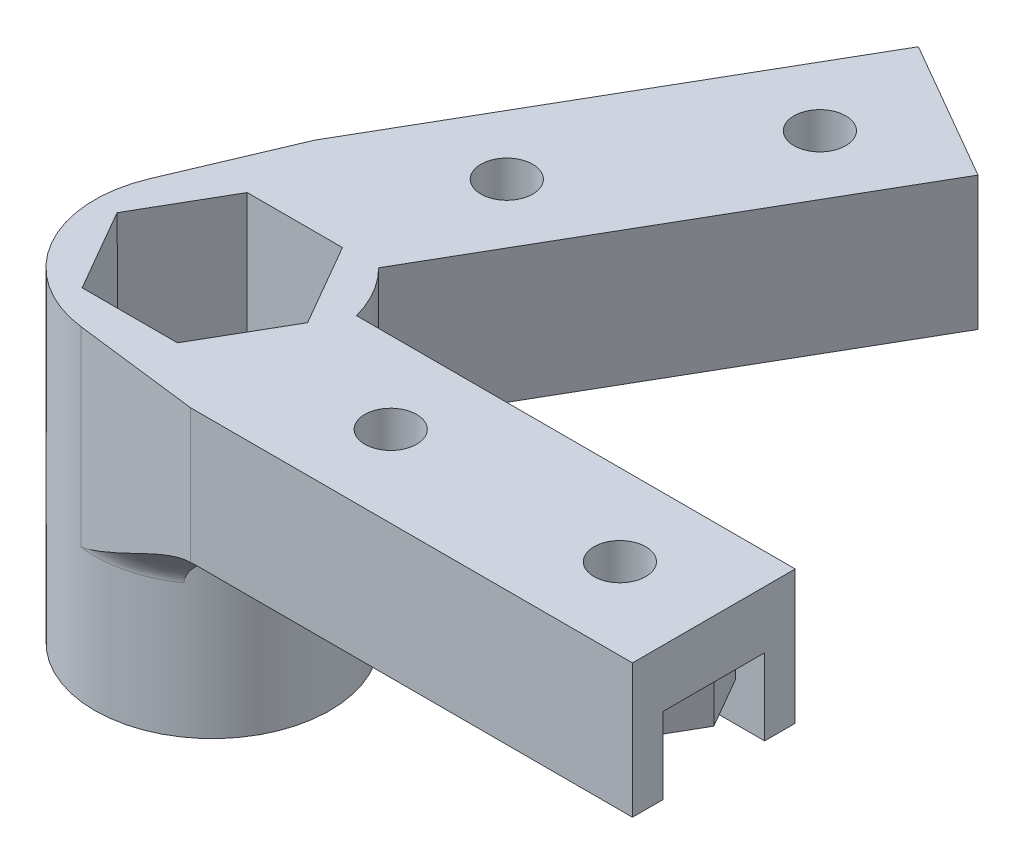
SolidWorks part; units mm, degrees
note: '?' marks a value the reader was unsure of.
ref_plane "Front Plane" through (0, 0, 0) normal (0, 0, 1) x (1, 0, 0)
ref_plane "Top Plane" through (0, 0, 0) normal (0, 1, 0) x (1, 0, 0)
ref_plane "Right Plane" through (0, 0, 0) normal (1, 0, 0) x (0, 0, -1)
sketch "Sketch1" plane through (0, 0, 0) normal (0, 1, 0) x (1, 0, 0)
  line L0 (57.15, 2.54) -> (57.15, -10.9855)
  line L2 (9.4434, 2.54) -> (57.15, 2.54)
  line L3 (-1.197, -9.7055) -> (9.1817, -10.9855)
  line L4 (9.1817, -10.9855) -> (57.15, -10.9855)
  circle A0 centre (0, 0) radius 5.0165
  arc A1 (9.4434, 2.54) -> (-1.197, -9.7055) centre (0, 0) ccw
  circle A4 centre (0, 0) radius 9.779 construction
  dimension "D1" = 4.7625
  dimension "D3" = 10.033
  dimension "D5" = 2.54
  dimension "D2" = 57.15
  dimension "D4" = 13.5255
extrude "Boss-Extrude1" add sketch "Sketch1" along normal blind 26.9875
sketch "Sketch18" plane through (0, 0, 0) normal (0, -1, 0) x (1, 0, 0)
  line L2 (57.15, 8.4455) -> (57.15, 0)
  line L3 (57.15, 0) -> (9.779, 0)
  line L6 (9.3378, 8.4455) -> (5.6391, 7.9893)
  line L7 (-1.197, 9.7055) -> (9.1817, 10.9855) construction
  line L9 (57.15, -2.54) -> (9.4434, -2.54) construction
  line L10 (57.15, 10.9855) -> (57.15, -2.54) construction
  line L11 (57.15, 8.4455) -> (9.3378, 8.4455)
  circle A2 centre (0, 0) radius 9.779
  arc A3 (9.779, 0) -> (5.6391, 7.9893) centre (0, 0) ccw
  dimension "D1" = 8.4455
  dimension "D2" = 2.54
  dimension "D3" = 4.7625
  dimension "D4" = 2.54
extrude "Cut-Extrude7" cut sketch "Sketch18" against normal blind 22.225
hole_wizard "#6 Clearance Hole1" positions "Sketch19" profile "Sketch20" hole size "#6" standard "ANSI Inch" end condition through all
sketch "Sketch19" plane through (0, 22.225, 0) normal (0, -1, 0) x (-1, 0, 0)
  line L0 (-9.779, 0) -> (-57.15, 0) construction
  point P0 (-19.05, -4.2227)
  point P2 (-38.1, -4.2227)
  dimension "D1" = 19.05
  dimension "D2" = 19.05
  dimension "D3" = 4.2227
sketch "Sketch20" plane through (19.05, 22.225, 4.2227) normal (1, 0, 0) x (0, 0, -1)
  line L0 (0, 0) -> (0, 4.7625)
  line L1 (0, 4.7625) -> (2.1526, 4.7625)
  line L2 (2.1526, 4.7625) -> (2.1526, 0)
  line L5 (2.1526, 0) -> (0, 0)
  line L11 (0, -6.35) -> (0, 107.95) construction
  dimension "Thru Hole Dia." = 4.3053
  dimension "Thru Hole Depth" = 4.7625
sketch "Sketch21" plane through (0, 22.225, 0) normal (0, -1, 0) x (1, 0, 0)
  line L1 (23.926, 4.2227) -> (21.488, 8.4455)
  line L2 (21.488, 8.4455) -> (16.612, 8.4455)
  line L3 (16.612, 8.4455) -> (14.174, 4.2227)
  line L4 (14.174, 4.2227) -> (16.612, 0)
  line L5 (16.612, 0) -> (21.488, 0)
  line L6 (21.488, 0) -> (23.926, 4.2227)
  line L7 (42.976, 4.2227) -> (40.538, 8.4455)
  line L8 (40.538, 8.4455) -> (35.662, 8.4455)
  line L9 (35.662, 8.4455) -> (33.224, 4.2227)
  line L10 (33.224, 4.2227) -> (35.662, 0)
  line L11 (35.662, 0) -> (40.538, 0)
  line L12 (40.538, 0) -> (42.976, 4.2227)
  line L13 (14.4123, 9.7155) -> (11.241, 4.2227)
  line L14 (11.241, 4.2227) -> (14.4123, -1.27)
  line L16 (23.6877, -1.27) -> (26.859, 4.2227)
  line L17 (26.859, 4.2227) -> (23.6877, 9.7155)
  line L19 (33.4623, 9.7155) -> (30.291, 4.2227)
  line L20 (30.291, 4.2227) -> (33.4623, -1.27)
  line L22 (42.7377, -1.27) -> (45.909, 4.2227)
  line L23 (45.909, 4.2227) -> (42.7377, 9.7155)
  line L25 (22.9545, 10.9855) -> (15.1455, 10.9855) construction
  line L26 (15.1455, -2.54) -> (22.9545, -2.54) construction
  line L27 (34.1955, -2.54) -> (42.0045, -2.54) construction
  line L28 (42.0045, 10.9855) -> (34.1955, 10.9855) construction
  line L29 (23.6877, 9.7155) -> (14.4123, 9.7155)
  line L30 (14.4123, -1.27) -> (23.6877, -1.27)
  line L31 (33.4623, -1.27) -> (42.7377, -1.27)
  line L32 (42.7377, 9.7155) -> (33.4623, 9.7155)
  line L33 (21.488, 9.7155) -> (16.612, 9.7155) construction
  line L34 (16.612, -1.27) -> (21.488, -1.27) construction
  line L35 (35.662, -1.27) -> (40.538, -1.27) construction
  line L36 (40.538, 9.7155) -> (35.662, 9.7155) construction
  line L37 (15.1455, 10.9855) -> (11.241, 4.2227) construction
  line L38 (26.859, 4.2227) -> (22.9545, 10.9855) construction
  line L39 (22.9545, -2.54) -> (26.859, 4.2227) construction
  line L40 (11.241, 4.2227) -> (15.1455, -2.54) construction
  line L41 (30.291, 4.2227) -> (34.1955, -2.54) construction
  line L42 (42.0045, -2.54) -> (45.909, 4.2227) construction
  line L43 (45.909, 4.2227) -> (42.0045, 10.9855) construction
  line L44 (34.1955, 10.9855) -> (30.291, 4.2227) construction
  circle A0 centre (19.05, 4.2227) radius 4.2228 construction
  circle A1 centre (38.1, 4.2227) radius 4.2227 construction
  dimension "D3" = 8.4455
  dimension "D1" = 2.54
  dimension "D2" = 1.27
extrude "Boss-Extrude6" add sketch "Sketch21" along normal blind 3.175
ref_axis "Axis1" through (0, 26.9875, 0) along (0, -1, 0)?
ref_plane "Plane1" through (0, 0, 0) normal (0.5, 0, 0.866) x (0, -1, 0)
mirror "Mirror1" about plane through (0, 0, 0) normal (0.5, 0, 0.866) of bodies 121 106 117
sketch "Sketch9" plane through (0, 0, 0) normal (0, 0, 1) x (1, 0, 0)
  line L1 (0, 26.9875) -> (0, 0) construction
  line L2 (57.15, 26.9875) -> (9.4434, 26.9875) construction
  circle A0 centre (63.5, 0) radius 26.9875
  dimension "D1" = 63.5
  dimension "D2" = 53.975
sketch "Sketch10" plane through (0, 0, -2.54) normal (0, 0, -1) x (-1, 0, 0)
  line L5 (-57.15, 26.9875) -> (-9.4434, 26.9875) construction
  line L6 (-57.15, 26.9875) -> (-50.0296, 26.9875)
  line L7 (-57.15, 26.9875) -> (-57.15, 0) construction
  line L8 (-57.15, 26.9875) -> (-57.15, 0)
  line L9 (-57.15, 0) -> (-9.4434, 0) construction
  line L10 (-57.15, 0) -> (-33.3375, 0)
  circle A3 centre (-63.5, 0) radius 30.1625
  arc A4 (-33.3375, 0) -> (-50.0296, 26.9875) centre (-63.5, 0) ccw
  dimension "D1" = 3.175
extrude "Boss-Extrude4" add sketch "Sketch10" along normal blind 15.875
sketch "Sketch11" plane through (0, 0, -2.54) normal (0, 0, -1) x (-1, 0, 0)
  circle A1 centre (-63.5, 0) radius 31.75
  circle A2 centre (-63.5, 0) radius 28.575
  circle A3 centre (-63.5, 0) radius 28.575
  dimension "D1" = 1.5875
  dimension "D2" = 3.175
extrude "Cut-Extrude1" cut sketch "Sketch11" along normal blind 12.7
extrude "Cut-Extrude2" cut sketch "Sketch9" against normal through all and the other way through all
sketch "Sketch13" plane through (0, 0, 0) normal (0, -1, 0) x (1, 0, 0)
  line L0 (28.575, -49.4934) -> (4.8895, -8.4689)
  line L1 (28.575, -49.4934) -> (30.7747, -48.2234)
  line L3 (30.7747, -48.2234) -> (6.9214, -6.9082)
  line L4 (30.7747, -48.2234) -> (6.9214, -6.9082) construction
  line L5 (9.779, 0) -> (30.1625, 0)
  line L7 (30.1625, 0) -> (30.1625, -2.54)
  line L8 (9.4434, -2.54) -> (30.1625, -2.54)
  line L10 (34.925, -2.54) -> (9.4434, -2.54) construction
  line L11 (36.5125, -18.415) -> (36.5125, 0) construction
  line L12 (9.779, 0) -> (36.5125, 0) construction
  line L13 (4.8895, -8.4689) -> (6.8395, -11.8464) construction
  line L14 (28.575, -49.4934) -> (30.7747, -48.2234) construction
  line L16 (-9.0037, -3.8161) -> (-4.9229, -13.4444) construction
  line L17 (-4.9229, -13.4444) -> (19.0613, -54.9861) construction
  line L19 (19.0613, -54.9861) -> (21.261, -53.7161) construction
  line L21 (-9.0037, -3.8161) -> (-4.9229, -13.4444)
  line L22 (-4.9229, -13.4444) -> (19.0613, -54.9861)
  line L24 (19.0613, -54.9861) -> (21.261, -53.7161)
  line L26 (9.3378, 8.4455) -> (5.6391, 7.9893) construction
  line L28 (-1.197, 9.7055) -> (9.1817, 10.9855) construction
  line L29 (57.15, 8.4455) -> (9.3378, 8.4455)
  line L30 (9.3378, 8.4455) -> (5.6391, 7.9893)
  line L31 (9.1817, 10.9855) -> (57.15, 10.9855)
  line L32 (-1.197, 9.7055) -> (9.1817, 10.9855)
  line L33 (57.15, 10.9855) -> (57.15, 8.4455)
  line L35 (9.1817, 10.9855) -> (36.5125, 10.9855) construction
  line L36 (57.15, 10.9855) -> (57.15, -18.415) construction
  line L38 (21.261, -53.7161) -> (-2.6451, -12.3095)
  line L39 (-2.6451, -12.3095) -> (-4.0994, -8.8783) construction
  line L40 (-2.6451, -12.3095) -> (-4.0994, -8.8783)
  arc A0 (4.8895, -8.4689) -> (6.9214, -6.9082) centre (0, 0) ccw
  arc A1 (9.779, 0) -> (9.4434, -2.54) centre (0, 0) cw
  arc A2 (6.9214, -6.9082) -> (9.4434, -2.54) centre (0, 0) ccw construction
  arc A3 (-9.0037, -3.8161) -> (-4.0994, -8.8783) centre (0, 0) ccw
  arc A4 (5.6391, 7.9893) -> (-1.197, 9.7055) centre (0, 0) ccw
  dimension "D1" = 6.35
extrude "Cut-Extrude4" cut sketch "Sketch13" against normal blind 15.875
fillet "Fillet2" radius 4.7625 4 edges at (9.6947, 15.875, -1.281) (5.9568, 15.875, -7.7554) (-7.0235, 15.875, -6.8044) (2.381, 15.875, 9.4847)
sketch "Sketch14" plane through (0, 0, 0) normal (0, 0, 1) x (1, 0, 0)
  line L0 (31.75, 0) -> (30.1625, 0)
  line L2 (30.1625, 15.875) -> (30.1625, 0)
  line L4 (30.1625, 0) -> (36.5125, 0) construction
  line L5 (30.1625, 15.875) -> (30.1625, 0) construction
  line L6 (41.6755, 15.875) -> (9.5275, 15.875) construction
  arc A0 (48.1907, 22.225) -> (36.5125, 0) centre (63.5, 0) ccw construction
  arc A1 (33.6678, 10.8674) -> (30.1625, 15.875) centre (30.1625, 12.1444) ccw
  arc A3 (33.6678, 10.8674) -> (31.75, 0) centre (63.5, 0) ccw
  dimension "D1" = 4.7625
extrude "Cut-Extrude5" cut sketch "Sketch14" against normal up to next
sketch "Sketch15" plane through (0, 26.9875, 0) normal (0, -1, 0) x (1, 0, 0)
  line L0 (13.4408, -45.2511) -> (19.0613, -54.9861)
  line L1 (13.4408, -45.2511) -> (25.1542, -38.4883)
  line L2 (19.0613, -54.9861) -> (30.7747, -48.2234)
  line L3 (25.1542, -38.4883) -> (30.7747, -48.2234)
  line L8 (28.575, -49.4934) -> (21.261, -53.7161) construction
  line L9 (-4.75, -13.7438) -> (19.0613, -54.9861) construction
  line L10 (30.7747, -48.2234) -> (9.3586, -11.1295) construction
extrude "Cut-Extrude6" cut sketch "Sketch15" against normal through all both and the other way through all
sketch "Sketch22" plane through (0, 26.9875, 0) normal (0, 1, 0) x (1, 0, 0)
  line L1 (7.9189, 0) -> (3.9595, 6.858)
  line L2 (3.9595, 6.858) -> (-3.9595, 6.858)
  line L3 (-3.9595, 6.858) -> (-7.9189, 0)
  line L4 (-7.9189, 0) -> (-3.9595, -6.858)
  line L5 (-3.9595, -6.858) -> (3.9595, -6.858)
  line L6 (3.9595, -6.858) -> (7.9189, 0)
  circle A0 centre (0, 0) radius 6.858 construction
  dimension "D1" = 13.716
extrude "Cut-Extrude8" cut sketch "Sketch22" against normal through all draft 0.4
ref_plane "Plane2" through (0, 0, 0) normal (0.5, 0, 0.866) x (0, -1, 0)
sketch "Sketch23" plane through (0, 0, 0) normal (0.5, 0, 0.866) x (0, -1, 0)
  line L1 (6.958, -23.441) -> (-39.4901, -23.441)
  line L2 (6.958, -23.441) -> (6.958, 66.6757)
  line L3 (6.958, 66.6757) -> (-39.4901, 66.6757)
  line L4 (-39.4901, -23.441) -> (-39.4901, 66.6757)
  line L5 (6.958, -23.441) -> (-39.4901, 66.6757) construction
  line L6 (6.958, 66.6757) -> (-39.4901, -23.441) construction
  point P0 (-16.2661, 21.6173)
extrude "Cut-Extrude9" cut sketch "Sketch23" along normal through all
mirror "Mirror2" about plane through (0, 0, 0) normal (0.5, 0, 0.866) of bodies 124
move or copy body "Body-Move/Copy2" [suppressed] bodies to move or copy 122
move or copy body "Body-Move/Copy1" [suppressed] bodies to move or copy 112
equation "\"D3@Sketch19\"=.3325/2"
